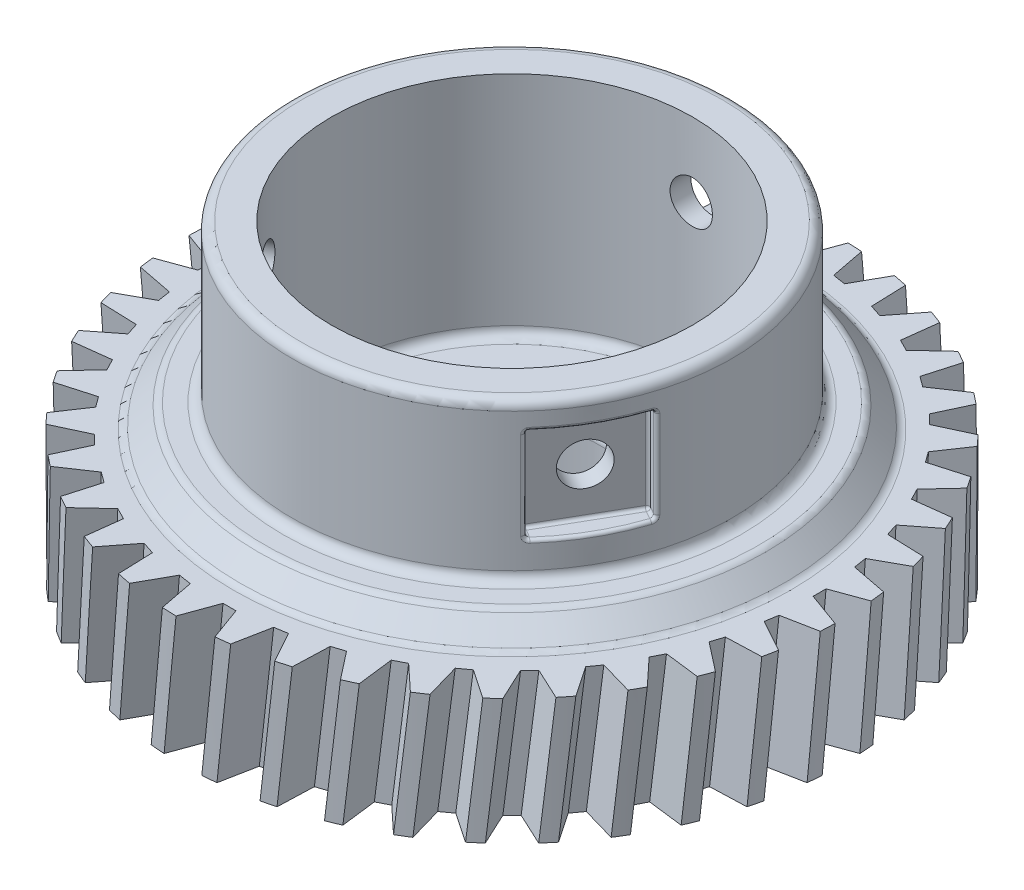
SolidWorks part; units mm, degrees
ref_plane "Спереди" through (0, 0, 0) normal (0, 0, 1) x (1, 0, 0)
ref_plane "Сверху" through (0, 0, 0) normal (0, 1, 0) x (1, 0, 0)
ref_plane "Справа" through (0, 0, 0) normal (1, 0, 0) x (0, 0, -1)
sketch "Эскиз1" plane through (0, 0, 0) normal (0, 1, 0) x (1, 0, 0)
  circle A0 centre (0, 0) radius 42
  circle A1 centre (0, 0) radius 23
  dimension "D1" = 46
  dimension "63" = 84
extrude "Бобышка-Вытянуть1" add sketch "Эскиз1" along normal blind 16
sketch "Эскиз7" plane through (0, 0, 0) normal (0, 1, 0) x (1, 0, 0)
  line L0 (0, 0) -> (43, 0) construction
  line L1 (37.6, -0.8246) -> (37.6, 0.8246)
  line L2 (43, -2.79) -> (43, 2.79)
  line L3 (37.6, 0.8246) -> (43, 2.79)
  line L4 (37.6, -0.8246) -> (43, -2.79)
  line L5 (40, 1.6981) -> (40, -1.6981) construction
  dimension "D1" = 43
  dimension "D2" = 37.6
  dimension "D3" = 20
  dimension "D4" = 5.58
  dimension "D5" = 40
ref_plane "Плоскость6" through (40, 0, 0) normal (1, 0, 0) x (0, 0, -1)
sketch "Эскиз8" plane through (40, 0, 0) normal (1, 0, 0) x (0, 0, -1)
  line L0 (0, 0) -> (0, 16) construction
  line L1 (42, 16) -> (-42, 16) construction
  line L2 (0, 0) -> (1.7182, 17.1833)
  dimension "D1" = 5.71
sweep "Вырез-По траектории4" cut profiles "Эскиз7" path "Эскиз8"
pattern_circular "Круговой массив4" count 40 over 360 about axis through (0, 16, 0) along (0, -1, 0) of "Вырез-По траектории4"
sketch "Эскиз9" plane through (0, 0, 0) normal (0, 1, 0) x (1, 0, 0)
  circle A0 centre (0, 0) radius 11.05
  circle A1 centre (0, 0) radius 23 construction
  circle A2 centre (0, 0) radius 23
  dimension "D1" = 22.1
extrude "Бобышка-Вытянуть2" add sketch "Эскиз9" along normal blind 10
sketch "Эскиз10" plane through (0, 10, 0) normal (0, 1, 0) x (1, 0, 0)
  circle A0 centre (0, 0) radius 17.45 construction
  circle A1 centre (0, 17.45) radius 3.2
  dimension "D1" = 34.9
  dimension "D2" = 6.4
extrude "Вырез-Вытянуть1" cut sketch "Эскиз10" against normal blind 7.5
pattern_circular "Круговой массив5" count 3 over 360 about axis through (0, 16, 0) along (0, -1, 0) of "Вырез-Вытянуть1"
sketch "Эскиз11" plane through (0, 0, 0) normal (0, 0, 1) x (1, 0, 0)
  line L0 (-23, 16) -> (-35, 16)
  line L3 (-28, 19) -> (-28, 39)
  line L4 (-28, 39) -> (-23, 39)
  line L5 (-23, 39) -> (-23, 16)
  line L6 (0, 0) -> (0, 70.2735) construction
  line L7 (-35, 16) -> (-32, 19)
  line L8 (-28, 19) -> (-32, 19)
  dimension "D1" = 12
  dimension "D2" = 45
  dimension "D3" = 5
  dimension "D4" = 20
  dimension "D5" = 3
revolve "Повернуть1" add sketch "Эскиз11" angle 360 about L6
fillet "Скругление1" radius 1.2 3 edges at (0, 19, -28) (0, 19, -32) (0, 16, -35)
ref_plane "Плоскость7" through (0, 0, -28) normal (0, 0, -1) x (-1, 0, 0)
sketch "Эскиз12" plane through (0, 0, -28) normal (0, 0, -1) x (-1, 0, 0)
  line L0 (0, 20.2) -> (0, 39) construction
  line L1 (6, 23.6) -> (-6, 23.6)
  line L2 (6, 23.6) -> (6, 35.6)
  line L3 (6, 35.6) -> (-6, 35.6)
  line L4 (-6, 23.6) -> (-6, 35.6)
  line L5 (6, 23.6) -> (-6, 35.6) construction
  line L6 (6, 35.6) -> (-6, 23.6) construction
  line L7 (28, 20.2) -> (-28, 20.2) construction
  line L8 (28, 39) -> (-28, 39) construction
  line L9 (0, 39) -> (0, 35.6) construction
  line L10 (0, 23.6) -> (0, 20.2) construction
  point P0 (0, 29.6)
  dimension "D1" = 12
extrude "Вырез-Вытянуть2" cut sketch "Эскиз12" against normal blind 2.5
sketch "Эскиз13" plane through (0, 0, -25.5) normal (0, 0, -1) x (-1, 0, 0)
  line L0 (0, 35.6) -> (0, 23.6) construction
  line L1 (6, 35.6) -> (-6, 35.6) construction
  line L2 (-6, 23.6) -> (6, 23.6) construction
  circle A0 centre (0, 29.6) radius 2.7
  dimension "D1" = 5.4
extrude "Вырез-Вытянуть3" cut sketch "Эскиз13" against normal up to next
pattern_circular "Круговой массив6" count 3 over 360 about axis through (0, 16, 0) along (0, -1, 0) of "Вырез-Вытянуть2", "Вырез-Вытянуть3" reverse direction yes
fillet "Скругление2" radius 1.2 1 edges at (0, 39, -28)
fillet "Скругление3" radius 0.4 32 edges at (0, 23.6, -28) (0, 35.6, -28) (0, 35.6, -25.5) (0, 23.6, -25.5) (6, 29.6, -25.5) (6, 29.6, -27.3496) (-6, 29.6, -25.5) (-6, 29.6, -27.3496) (24.2487, 23.6, 14) (22.0836, 23.6, 12.75) (20.6854, 29.6, 18.8709) (19.0836, 29.6, 17.9462) (19.8845, 23.6, 18.4085) (24.2487, 35.6, 14) (22.0836, 35.6, 12.75) (19.8845, 35.6, 18.4085) (26.6854, 29.6, 8.4786) (25.8845, 23.6, 8.0162) (25.0836, 29.6, 7.5538) (25.8845, 35.6, 8.0162) (-26.6854, 29.6, 8.4786) (-25.0836, 29.6, 7.5538) (-24.2487, 35.6, 14) (-22.0836, 35.6, 12.75) (-25.8845, 35.6, 8.0162) (-24.2487, 23.6, 14) (-25.8845, 23.6, 8.0162) (-22.0836, 23.6, 12.75) (-20.6854, 29.6, 18.8709) (-19.8845, 23.6, 18.4085) (-19.0836, 29.6, 17.9462) (-19.8845, 35.6, 18.4085)
fillet "Скругление4" radius 1.2 3 edges at (0, 0, 11.05) (0, 10, 11.05) (0, 10, 23)
